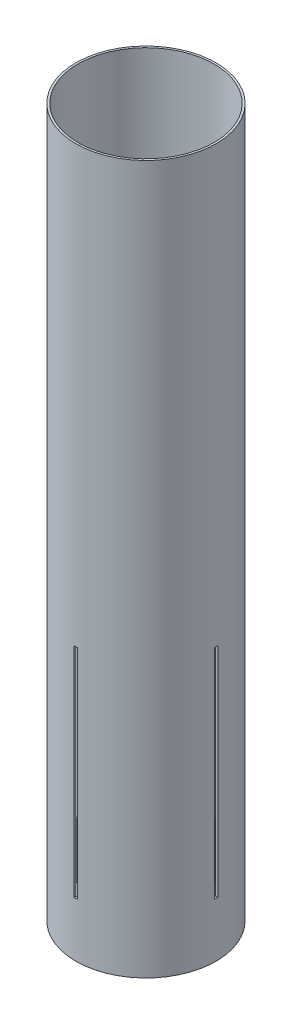
SolidWorks part; units mm, degrees
ref_plane "Front Plane" through (0, 0, 0) normal (0, 0, 1) x (1, 0, 0)
ref_plane "Top Plane" through (0, 0, 0) normal (0, 1, 0) x (1, 0, 0)
ref_plane "Right Plane" through (0, 0, 0) normal (1, 0, 0) x (0, 0, -1)
sketch "Sketch1" plane through (0, 0, 0) normal (0, 1, 0) x (1, 0, 0)
  circle A0 centre (0, 0) radius 65.405
  circle A1 centre (0, 0) radius 63.5
  dimension "D1" = 130.81
  dimension "D2" = 127
extrude "Boss-Extrude1" add sketch "Sketch1" along normal mid plane 660.4
sketch "Sketch4" plane through (0, 0, 0) normal (1, 0, 0) x (0, 0, -1)
  line L0 (0, -330.2) -> (0, 330.2)
  line L1 (-1.5875, -76.2) -> (1.5875, -76.2)
  line L2 (-1.5875, -76.2) -> (-1.5875, -279.4)
  line L3 (-1.5875, -279.4) -> (1.5875, -279.4)
  line L4 (1.5875, -76.2) -> (1.5875, -279.4)
  line L5 (-65.405, -330.2) -> (65.405, -330.2) construction
  line L6 (65.405, 330.2) -> (-65.405, 330.2) construction
  line L7 (-63.5, -330.2) -> (63.5, -330.2) construction
  line L8 (65.405, -330.2) -> (65.405, 330.2) construction
  dimension "D1" = 3.175
  dimension "D2" = 203.2
  dimension "D3" = 50.8
  dimension "D4" = 63.8175
extrude "Cut-Extrude2" cut sketch "Sketch4" along direction (1, 0, 0) on the side against the normal through all both and the other way through all contours L2 L3 L4 L1
pattern_circular "CirPattern4" count 2 every 90 about axis through (0, 330.2, 0) along (0, -1, 0) of "Cut-Extrude2" reverse direction yes
equation "\"iDiameter\"= 5in"
equation "\"oDiameter\"= 5.15in"
equation "\"length\"= 26in"
